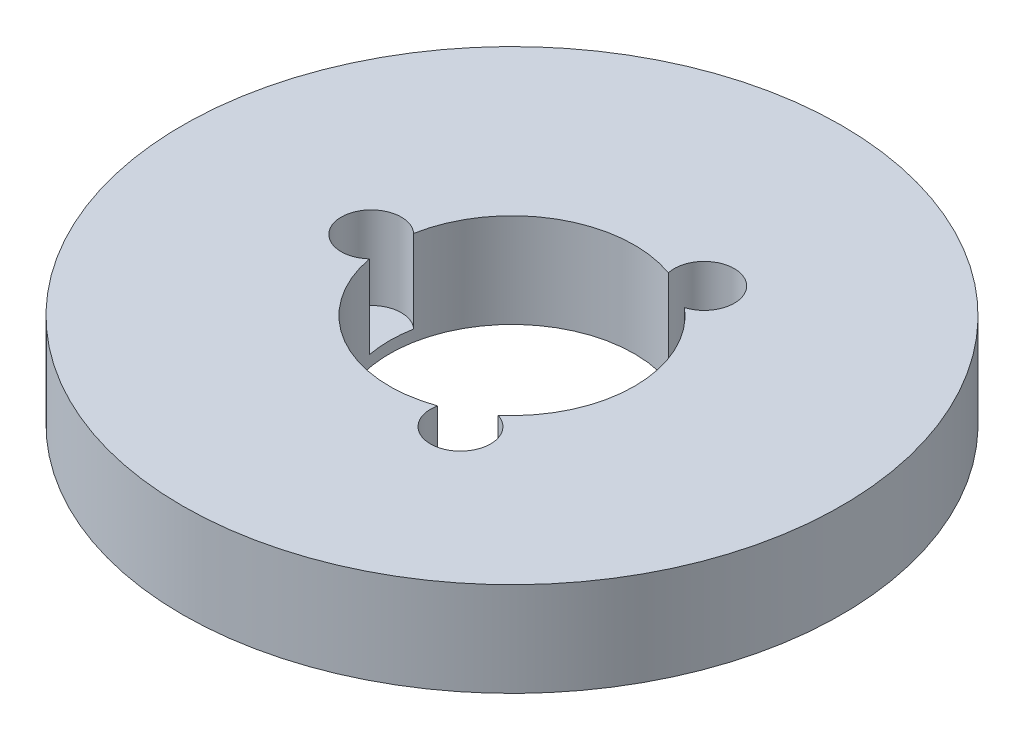
SolidWorks part; units mm, degrees
ref_plane "Front Plane" through (0, 0, 0) normal (0, 0, 1) x (1, 0, 0)
ref_plane "Top Plane" through (0, 0, 0) normal (0, 1, 0) x (1, 0, 0)
ref_plane "Right Plane" through (0, 0, 0) normal (1, 0, 0) x (0, 0, -1)
sketch "Sketch1" plane through (0, 0, 0) normal (0, 1, 0) x (1, 0, 0)
  circle A0 centre (0, 0) radius 87.5
  dimension "FLANGE_OD" = 175
extrude "Boss-Extrude1" add sketch "Sketch1" along normal blind 25
sketch "Sketch2" plane through (0, 0, 0) normal (0, 1, 0) x (1, 0, 0)
  circle A0 centre (0, 0) radius 32.5
  dimension "BORE_D" = 65
extrude "Cut-Extrude1" cut sketch "Sketch2" along normal through all
sketch "Sketch3" plane through (0, 25, 0) normal (0, 1, 0) x (1, 0, 0)
  circle A0 centre (0, 0) radius 37.3646 construction
  circle A1 centre (-37.3646, 0) radius 7.9758
  dimension "BOLT_D" = 15.9515
  dimension "BOLT_PCD" = 74.7293
extrude "Cut-Extrude2" cut sketch "Sketch3" against normal blind 21.986
pattern_circular "CirPattern1" count 3 over 360 about axis through (0, 0, 0) along (0, 1, 0) of "Cut-Extrude2"
